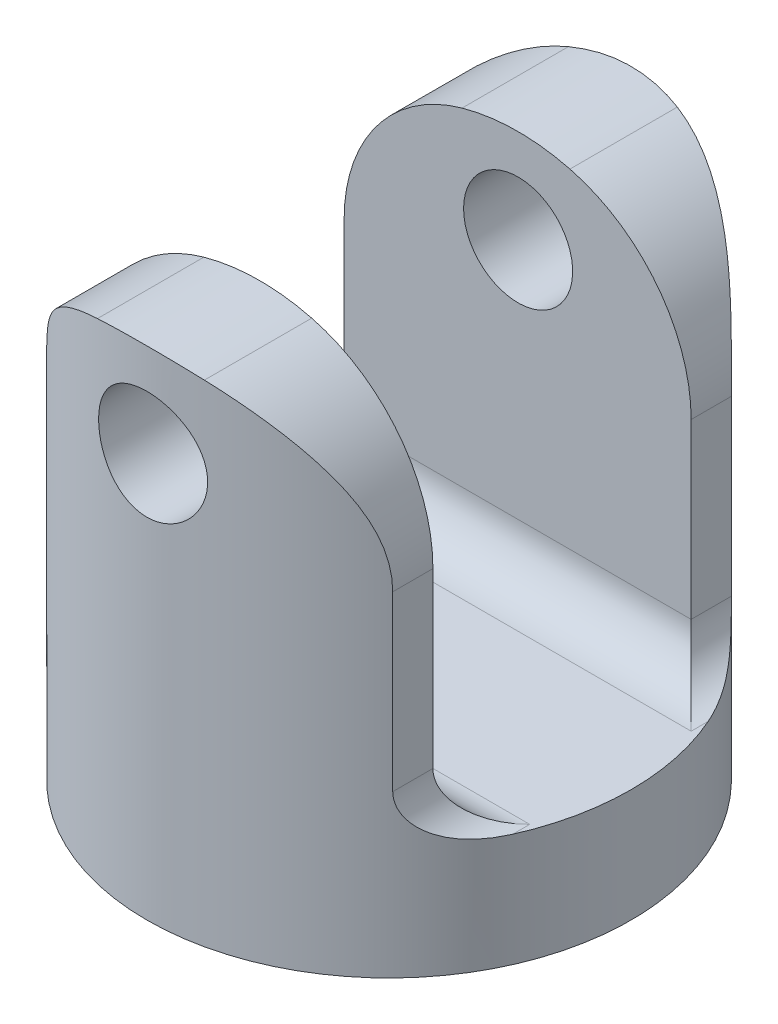
SolidWorks part; units mm, degrees
material "1060 Alloy"
ref_plane "Front Plane" through (0, 0, 0) normal (0, 0, 1) x (1, 0, 0)
ref_plane "Top Plane" through (0, 0, 0) normal (0, 1, 0) x (1, 0, 0)
ref_plane "Right Plane" through (0, 0, 0) normal (1, 0, 0) x (0, 0, -1)
sketch "Sketch1" plane through (0, 0, 0) normal (0, 1, 0) x (1, 0, 0)
  circle A0 centre (0, 0) radius 15
  dimension "D1" = 30
extrude "Boss-Extrude1" add sketch "Sketch1" along normal blind 10
sketch "Sketch2" plane through (0, 0, 0) normal (0, 0, 1) x (1, 0, 0)
  line L0 (-10.7808, 10) -> (10.7221, 10)
  line L1 (15, 10) -> (-15, 10) construction
  line L2 (10.7221, 10) -> (10.7221, 25.0886)
  line L4 (-10.7808, 25) -> (-10.7808, 10)
  line L5 (0, 0) -> (0, 17.9155) construction
  arc A0 (-10.7808, 25) -> (10.7221, 25.0886) centre (0, 17.9155) cw
  dimension "D1" = 15
extrude "Boss-Extrude2" add sketch "Sketch2" along normal up to surface and the other way up to surface up to face at (0, 10, 15) other way up to face at (0, 10, 15)
sketch "Sketch3" plane through (10.7221, 0, 0) normal (1, 0, 0) x (0, 0, -1)
  line L0 (10.4899, 10) -> (-10.4899, 10) construction
  line L1 (-8, 10) -> (8, 10)
  line L2 (-8, 10) -> (-8, 60)
  line L3 (-8, 60) -> (8, 60)
  line L4 (8, 10) -> (8, 60)
  line L5 (0, 0) -> (0, 10) construction
  dimension "D1" = 16
  dimension "D2" = 50
extrude "Cut-Extrude1" cut sketch "Sketch3" against normal through all
sketch "Sketch4" plane through (0, 0, 8) normal (0, 0, -1) x (-1, 0, 0)
  line L0 (0, 25) -> (0, 0) construction
  circle A0 centre (0, 25) radius 3.3782
extrude "Cut-Extrude2" cut sketch "Sketch4" against normal through all and the other way through all
sketch "Sketch5" plane through (0, 10, 0) normal (0, 1, 0) x (1, 0, 0)
  line L0 (10.7221, -8) -> (-10.7808, -8) construction
  line L1 (-10.7808, 8) -> (10.7221, 8)
  line L3 (-10.7808, -8) -> (10.7221, -8)
  line L5 (-10.7808, 8) -> (10.7221, 8) construction
  line L6 (-10.7808, 8) -> (10.7221, 8) construction
  line L7 (-10.7808, -8) -> (-10.7808, -12.7535)
  line L8 (-10.7808, 10.4295) -> (-20.8179, 10.4295)
  line L9 (-10.7808, 10.4295) -> (-10.7808, 8)
  line L10 (-10.7808, -12.7535) -> (-20.8179, -12.7535)
  line L11 (-20.8179, 10.4295) -> (-20.8179, -12.7535)
  line L12 (10.7221, 10.4899) -> (25.3558, 10.4899)
  line L13 (10.7221, 10.4899) -> (10.7221, 8)
  line L14 (10.7221, -11.5434) -> (25.3558, -11.5434)
  line L15 (25.3558, 10.4899) -> (25.3558, -11.5434)
  line L16 (10.7221, -8) -> (10.7221, -11.5434)
extrude "Cut-Extrude3" cut sketch "Sketch5" against normal blind 3
fillet "Fillet1" radius 10 4 edges at (-10.7808, 25, 9.2147) (-10.7808, 25, -9.2147) (10.7221, 25.0886, -9.2449) (10.7221, 25.0886, 9.2449)
fillet "Fillet2" radius 3 6 edges at (-10.7808, 7, 9.2147) (-10.7808, 7, -9.2147) (10.7221, 7, 9.2449) (10.7221, 7, -9.2449) (-0.0294, 7, -8) (-0.0294, 7, 8)
